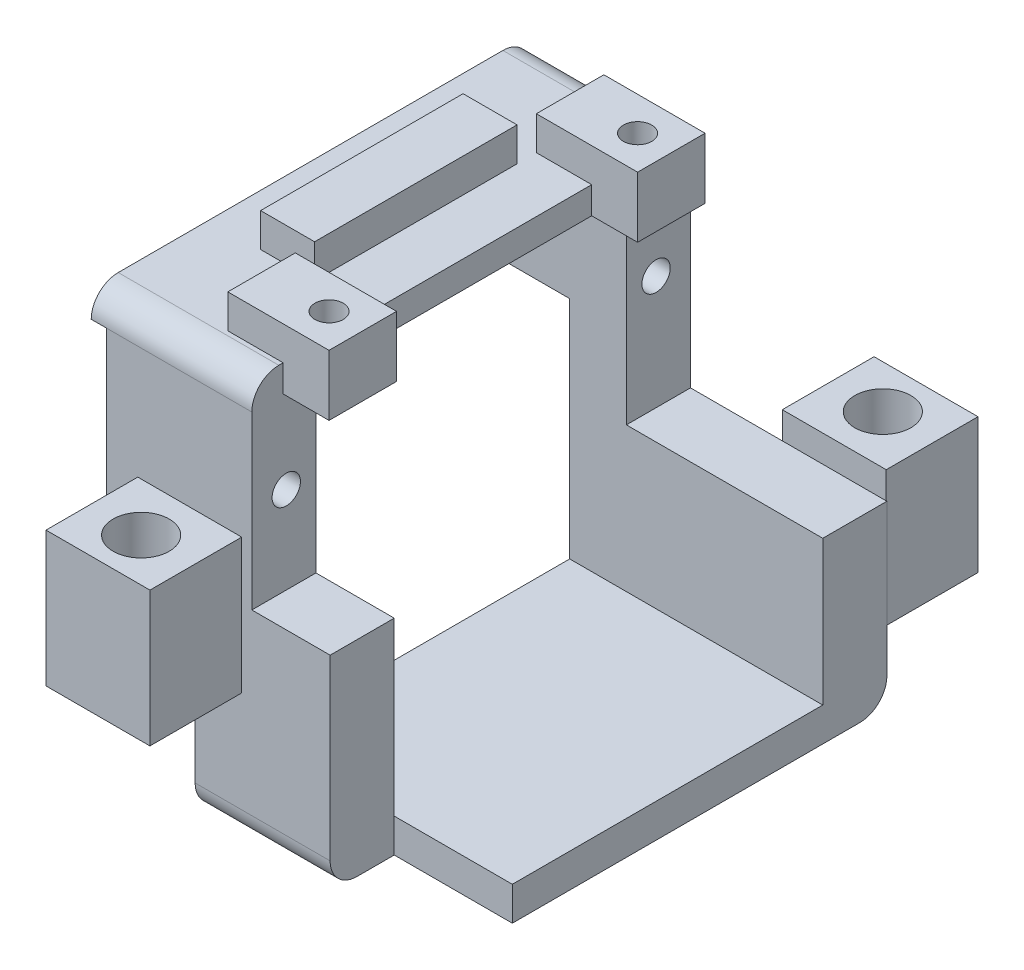
SolidWorks part; units mm, degrees
ref_plane "Front Plane" through (0, 0, 0) normal (0, 0, 1) x (1, 0, 0)
ref_plane "Top Plane" through (0, 0, 0) normal (0, 1, 0) x (1, 0, 0)
ref_plane "Right Plane" through (0, 0, 0) normal (1, 0, 0) x (0, 0, -1)
sketch "Sketch1" plane through (0, 0, 0) normal (0, 1, 0) x (1, 0, 0)
  line L0 (-1.1, 16.25) -> (-1.1, 11.5)
  line L1 (-17.65, -16.25) -> (17.65, -16.25)
  line L2 (-17.65, -16.25) -> (-17.65, 16.25)
  line L3 (-17.65, 16.25) -> (17.65, 16.25)
  line L4 (17.65, -16.25) -> (17.65, 16.25)
  line L5 (-17.65, -16.25) -> (17.65, 16.25) construction
  line L6 (-17.65, 16.25) -> (17.65, -16.25) construction
  line L7 (-1.1, 11.5) -> (17.65, 11.5)
  line L8 (-1.1, -16.25) -> (-1.1, -11.5)
  line L9 (-1.1, -11.5) -> (17.65, -11.5)
  line L10 (-1.1, 11.5) -> (-1.1, -11.5) construction
  line L11 (8.9, -11.5) -> (8.9, -16.25)
  line L12 (-8.8, 16.25) -> (-8.8, 11.5)
  line L13 (-8.8, 11.5) -> (-3.8, 11.5)
  line L14 (-3.8, 11.5) -> (-3.8, 16.25)
  line L15 (-3.8, -16.25) -> (-3.8, -11.5)
  line L16 (-3.8, -11.5) -> (-8.8, -11.5)
  line L17 (-8.8, -11.5) -> (-8.8, -16.25)
  line L18 (-8.8, 11.5) -> (-8.8, -11.5)
  line L19 (17.6, 16.25) -> (17.6, 23.05)
  line L20 (17.6, 23.05) -> (9.9, 23.05)
  line L21 (9.9, 23.05) -> (9.9, 16.25)
  line L22 (-5.35, -16.25) -> (-5.35, -23.05)
  line L23 (-5.35, -23.05) -> (2.35, -23.05)
  line L24 (2.35, -23.05) -> (2.35, -16.25)
  line L28 (-1.1, 11.5) -> (-1.1, -11.5)
  circle A0 centre (13.75, 19.85) radius 2.075
  circle A2 centre (-1.5, -19.85) radius 2.075
  point P0 (0, 0)
  point P11 (-1.1, 0)
  point P31 (13.75, 23.05)
  point P45 (-1.5, -23.05)
  dimension "D11" = 4.15
  dimension "D19" = 4.15
  dimension "D1" = 32.5
  dimension "D2" = 23
  dimension "D3" = 8.75
  dimension "D4" = 10
  dimension "D5" = 16.55
  dimension "D6" = 2.7
  dimension "D7" = 5
  dimension "D8" = 13.75
  dimension "D9" = 7.7
  dimension "D10" = 6.8
  dimension "D12" = 1.5
  dimension "D13" = 19.85
  dimension "D16" = 7.7
  dimension "D17" = 6.8
  dimension "D20" = 19.85
extrude "Boss-Extrude1" add sketch "Sketch1" against normal blind 2.5 contours L7 L28 L9 L4 | L0 L7 L4 L3 | L11 L9 L8 L1 region at (8.275, 0, -13.875) region at (8.275, 0, 0) region at (3.9, 0, 13.875)
extrude "Boss-Extrude2" add sketch "Sketch1<3>" along normal blind 12.7 contours L0 L7 L4 L3 | L11 L9 L8 L1 region at (8.275, 0, -13.875) region at (3.9, 0, 13.875)
sketch "Sketch1<3>" plane through (0, 0, 0) normal (0, 1, 0) x (1, 0, 0) same geometry as "Sketch1"
sketch "Sketch3" plane through (0, 0, 0) normal (0, 1, 0) x (1, 0, 0)
  line L0 (3.1, 16.25) -> (3.1, 11.5)
  line L1 (-17.65, 16.25) -> (17.65, 16.25) construction
  line L2 (-1.1, 11.5) -> (17.65, 11.5) construction
  line L3 (3.1, 11.5) -> (-17.65, 11.5)
  line L4 (-17.65, -16.25) -> (-17.65, 16.25) construction
  line L5 (3.1, -16.25) -> (3.1, -11.5)
  line L6 (-17.65, -16.25) -> (17.65, -16.25) construction
  line L7 (-1.1, -11.5) -> (17.65, -11.5) construction
  line L8 (3.1, -11.5) -> (-17.65, -11.5)
  line L9 (3.1, 11.5) -> (3.1, -11.5)
  line L10 (-7.65, -11.5) -> (-7.65, -16.275)
  line L11 (3.1, 16.25) -> (-17.65, 16.25)
  line L12 (-17.65, 16.25) -> (-17.65, 11.5)
  line L13 (-17.65, -11.5) -> (-17.65, -16.25)
  line L14 (-17.65, -16.25) -> (3.1, -16.25)
  line L15 (-8.8, 11.5) -> (-8.8, -11.5)
  line L16 (-8.8, 11.5) -> (-8.8, 16.25)
  line L17 (-8.8, -11.5) -> (-8.8, -16.25)
  dimension "D1" = 20.75
  dimension "D2" = 10
extrude "Boss-Extrude3" add sketch "Sketch3" along normal blind 12.7 from surface contours L11 L12 L3 L0 | L10 L14 L5 L8 region at (-2.85, 0, -13.875) region at (-2.275, 0, 13.875) starting at face at (8.275, 12.7, -13.875)
extrude "Boss-Extrude4" add sketch "Sketch3<3>" along normal blind 2 from surface contours L16 L3 L0 L11 | L3 L15 L8 L9 | L10 L14 L5 L8 | L8 L17 L14 L10 region at (-2.85, 0, -13.875) region at (-2.85, 0, 0) region at (-2.275, 0, 13.875) region at (-8.225, 0, 13.875) starting at face at (-2.275, 25.4, 13.875)
sketch "Sketch3<3>" plane through (0, 0, 0) normal (0, 1, 0) x (1, 0, 0) same geometry as "Sketch3"
sketch "Sketch2" plane through (0, 0, 0) normal (1, 0, 0) x (0, 0, -1)
  line L0 (13.7, 6.45) -> (-13.7, 6.45) construction
  line L1 (-13.7, 19.15) -> (13.7, 19.15) construction
  circle A0 centre (13.7, 6.45) radius 1.05
  circle A1 centre (-13.7, 6.45) radius 1.05
  circle A2 centre (-13.7, 19.15) radius 1.05
  circle A3 centre (13.7, 19.15) radius 1.05
  point P4 (0, 6.45)
  dimension "D1" = 2.1
  dimension "D2" = 2.1
  dimension "D6" = 2.1
  dimension "D7" = 2.1
  dimension "D3" = 27.4
  dimension "D4" = 6.45
  dimension "D5" = 6.45
extrude "Cut-Extrude1" cut sketch "Sketch2" along normal blind 8 from surface contours A1 | A0 region at (0, 6.45, -13.7) region at (0, 6.45, 13.7) starting at face at (-1.1, 5.725, 0)
extrude "Cut-Extrude2" cut sketch "Sketch2<3>" against normal blind 8 from surface contours A3 | A2 region at (0, 19.15, 13.7) region at (0, 19.15, -13.7) starting at face at (3.1, 19.55, 0)
sketch "Sketch2<3>" plane through (0, 0, 0) normal (1, 0, 0) x (0, 0, -1) same geometry as "Sketch2"
extrude "Boss-Extrude5" add sketch "Sketch1<4>" along normal blind 10 from offset 7 contours L23 L24 L1 L22 A2 region at (0.625, 0, 16.3527)
sketch "Sketch1<4>" plane through (0, 0, 0) normal (0, 1, 0) x (1, 0, 0) same geometry as "Sketch1"
extrude "Boss-Extrude6" add sketch "Sketch1<7>" against normal blind 10 from surface contours L20 L21 L3 L19 A0 region at (10.0027, 0, -19.65) starting at face at (10.375, 12.7, -13.875)
sketch "Sketch1<7>" plane through (0, 0, 0) normal (0, 1, 0) x (1, 0, 0) same geometry as "Sketch1"
fillet "Fillet1" radius 2 4 edges at (3.9, -2.5, 16.25) (-2.85, 27.4, 16.25) (8.275, -2.5, -16.25) (-2.85, 27.4, -16.25)
sketch "Sketch5" plane through (0, 0, 0) normal (0, 1, 0) x (1, 0, 0)
  line L1 (17.65, 16.25) -> (3.1, 16.25)
  line L2 (17.65, 16.25) -> (17.65, 11.5)
  line L3 (17.65, 11.5) -> (3.1, 11.5)
  line L4 (3.1, 16.25) -> (3.1, 11.5)
extrude "Cut-Extrude3" cut sketch "Sketch5" against normal blind 2 from surface starting at face at (12.0625, 12.7, -16.7625)
sketch "Sketch6" plane through (0, 0, 0) normal (0, 1, 0) x (1, 0, 0)
  line L1 (-8.8, 11.5) -> (-1.1, 11.5)
  line L2 (-8.8, 11.5) -> (-8.8, 16.25)
  line L3 (-8.8, 16.25) -> (-1.1, 16.25)
  line L4 (-1.1, 11.5) -> (-1.1, 16.25)
extrude "Cut-Extrude4" cut sketch "Sketch6" along normal blind 4 from surface starting at face at (-4.95, 12.7, -13.875)
sketch "Sketch7" plane through (0, 0, 0) normal (0, 1, 0) x (1, 0, 0)
  line L0 (4, 11.43) -> (4, -11.43) construction
  line L2 (1.5, 13.93) -> (6.5, 13.93)
  line L3 (1.5, 13.93) -> (1.5, 8.93)
  line L4 (1.5, 8.93) -> (6.5, 8.93)
  line L5 (6.5, 13.93) -> (6.5, 8.93)
  line L6 (1.5, 13.93) -> (6.5, 8.93) construction
  line L7 (1.5, 8.93) -> (6.5, 13.93) construction
  line L8 (1.5, -8.93) -> (6.5, -8.93)
  line L9 (1.5, -8.93) -> (1.5, -13.93)
  line L10 (1.5, -13.93) -> (6.5, -13.93)
  line L11 (6.5, -8.93) -> (6.5, -13.93)
  line L12 (1.5, -8.93) -> (6.5, -13.93) construction
  line L13 (1.5, -13.93) -> (6.5, -8.93) construction
  line L21 (-5, -7.5) -> (-1, -7.5)
  line L22 (-5, -7.5) -> (-5, 7.5)
  line L23 (-5, 7.5) -> (-1, 7.5)
  line L24 (-1, -7.5) -> (-1, 7.5)
  line L25 (-5, -7.5) -> (-1, 7.5) construction
  line L26 (-5, 7.5) -> (-1, -7.5) construction
  line L27 (1.5, 13.93) -> (-1, 13.93)
  line L28 (1.5, 13.93) -> (1.5, 8.93)
  line L29 (1.5, 8.93) -> (-1, 8.93)
  line L30 (-1, 13.93) -> (-1, 8.93)
  line L31 (1.5, -13.93) -> (-1, -13.93)
  line L32 (1.5, -13.93) -> (1.5, -8.93)
  line L33 (1.5, -8.93) -> (-1, -8.93)
  line L34 (-1, -13.93) -> (-1, -8.93)
  circle A0 centre (4, 11.43) radius 1.05
  circle A1 centre (4, -11.43) radius 1.05
  point P4 (4, 0)
  point P14 (-3, 0)
  dimension "D1" = 2.1
  dimension "D2" = 2.1
  dimension "D3" = 22.86
  dimension "D4" = 5
  dimension "D5" = 5
  dimension "D6" = 5
  dimension "D7" = 5
  dimension "D8" = 4
  dimension "D9" = 3
  dimension "D10" = 15
  dimension "D11" = 4
extrude "Boss-Extrude7" add sketch "Sketch7" along normal blind 2.5 and the other way blind 2 from surface contours L21 L24 L23 L22 | L11 L8 L9 L10 A1 | L34 L31 L9 L33 | L27 L30 L29 L3 | L5 L2 L3 L4 A0 region at (4, 0, -13.8593) region at (0.25, 0, -11.43) region at (4, 0, 9.0007) region at (0.25, 0, 11.43) region at (-3, 0, 0) starting at face at (-2.85, 27.4, 0)
